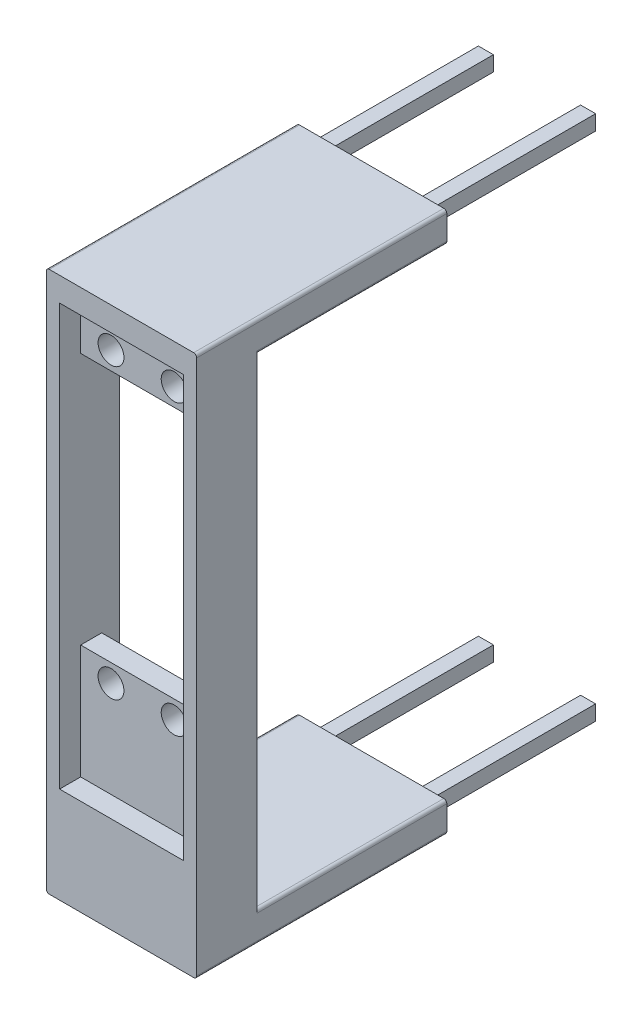
SolidWorks part; units mm, degrees
ref_plane "Front Plane" through (0, 0, 0) normal (0, 0, 1) x (1, 0, 0)
ref_plane "Top Plane" through (0, 0, 0) normal (0, 1, 0) x (1, 0, 0)
ref_plane "Right Plane" through (0, 0, 0) normal (1, 0, 0) x (0, 0, -1)
sketch "Sketch2" plane through (0, 0, -60.1331) normal (0, 0, 1) x (1, 0, 0)
  line L0 (165.5709, -7.7744) -> (110.5709, -7.7744) construction
  line L5 (113.0709, -2.7744) -> (138.0709, -2.7744)
  line L6 (113.0709, -2.7744) -> (113.0709, -7.7744)
  line L7 (113.0709, -7.7744) -> (138.0709, -7.7744)
  line L8 (138.0709, -2.7744) -> (138.0709, -7.7744)
  line L9 (110.5709, -2.7744) -> (160.5709, -2.7744) construction
  line L10 (165.5709, 82.2256) -> (110.5709, 82.2256) construction
  line L11 (113.0709, 82.2256) -> (138.0709, 82.2256)
  line L12 (113.0709, 82.2256) -> (113.0709, 77.2256)
  line L13 (113.0709, 77.2256) -> (138.0709, 77.2256)
  line L14 (138.0709, 82.2256) -> (138.0709, 77.2256)
  line L17 (115.5709, -5.2744) -> (113.0709, -5.2744)
  line L18 (115.5709, -3.7744) -> (115.5709, -6.7744) construction
  line L19 (135.5709, -5.2744) -> (138.0709, -5.2744)
  line L20 (160.5709, 77.2256) -> (110.5709, 77.2256) construction
  line L21 (135.5709, -3.7744) -> (135.5709, -6.7744) construction
  line M13 (165.5709, 82.2256) -> (110.5709, 82.2256)
  line M15 (110.5709, 77.2256) -> (160.5709, 77.2256)
  line M19 (160.5709, -2.7744) -> (110.5709, -2.7744)
  line M21 (110.5709, -7.7744) -> (165.5709, -7.7744)
  line M23 (115.5709, -3.7744) -> (118.5709, -3.7744)
  line M24 (118.5709, -3.7744) -> (118.5709, -6.7744)
  line M25 (118.5709, -6.7744) -> (115.5709, -6.7744)
  line M26 (115.5709, -6.7744) -> (115.5709, -3.7744)
  line M27 (132.5709, 81.2256) -> (135.5709, 81.2256)
  line M28 (135.5709, 81.2256) -> (135.5709, 78.2256)
  line M29 (135.5709, 78.2256) -> (132.5709, 78.2256)
  line M30 (132.5709, 78.2256) -> (132.5709, 81.2256)
  line M31 (115.5709, 81.2256) -> (118.5709, 81.2256)
  line M32 (118.5709, 81.2256) -> (118.5709, 78.2256)
  line M33 (118.5709, 78.2256) -> (115.5709, 78.2256)
  line M34 (115.5709, 78.2256) -> (115.5709, 81.2256)
  line M35 (132.5709, -3.7744) -> (135.5709, -3.7744)
  line M36 (135.5709, -3.7744) -> (135.5709, -6.7744)
  line M37 (135.5709, -6.7744) -> (132.5709, -6.7744)
  line M38 (132.5709, -6.7744) -> (132.5709, -3.7744)
  dimension "D1" = 25
extrude "Boss-Extrude1" add sketch "Sketch2" along normal up to surface (31.5956 mm away) contours L8 L6 M38 M35 M36 M19 M26 M23 M24 M25 M21 M37 | L14 L12 M13 M15 M34 M31 M32 M33 M30 M27 M28 M29 region at (125.5709, -5.2744, -60.1331) region at (125.5709, 79.7256, -60.1331)
sketch "Sketch3" plane through (0, 0, -60.1331) normal (0, 0, 1) x (1, 0, 0)
  line L0 (165.5709, -7.7744) -> (110.5709, -7.7744) construction
  line L1 (113.0709, 82.2256) -> (138.0709, 82.2256)
  line L2 (113.0709, 82.2256) -> (113.0709, -7.7744)
  line L3 (113.0709, -7.7744) -> (138.0709, -7.7744)
  line L4 (138.0709, 82.2256) -> (138.0709, -7.7744)
sketch "Sketch4" plane through (0, 0, -28.5375) normal (0, 0, 1) x (1, 0, 0)
  line L1 (113.0709, 82.2256) -> (138.0709, 82.2256)
  line L2 (113.0709, 82.2256) -> (113.0709, -7.7744)
  line L3 (113.0709, -7.7744) -> (138.0709, -7.7744)
  line L4 (138.0709, 82.2256) -> (138.0709, -7.7744)
extrude "Boss-Extrude3" add sketch "Sketch4" along normal blind 10
sketch "Sketch6" plane through (0, 0, -18.5375) normal (0, 0, 1) x (1, 0, 0)
  line L0 (113.0709, 82.2256) -> (138.0709, 82.2256) construction
  line L2 (113.0709, 82.2256) -> (113.0709, -7.7744) construction
  line L3 (138.0709, 82.2256) -> (138.0709, -7.7744) construction
  circle A2 centre (120.3209, 72.2256) radius 2.15
  circle A3 centre (130.8209, 72.2256) radius 2.15
  circle A4 centre (130.8209, 24.2256) radius 2.15
  circle A5 centre (120.3209, 24.2256) radius 2.15
  circle A6 centre (130.8209, 72.2256) radius 2.15
  point P2 (0, 0)
  point P3 (0, 0)
  point P6 (0, 0)
  point P10 (0, 0)
  dimension "D1" = 4.3
  dimension "D2" = 10
  dimension "D3" = 7.25
  dimension "D4" = 10.5
  dimension "D5" = 48
  dimension "D6" = 48
  dimension "D7" = 10.5
  dimension "D8" = 7.25
extrude "Cut-Extrude2" cut sketch "Sketch6" against normal blind 10 contours A4 | A5 | A6 | A2 region at (120.3209, 72.2256, -18.5375) region at (130.8209, 72.2256, -18.5375) region at (130.8209, 24.2256, -18.5375) region at (120.3209, 24.2256, -18.5375)
sketch "Sketch7" plane through (0, 0, -18.5375) normal (0, 0, 1) x (1, 0, 0)
  line L5 (120.3209, 24.2256) -> (120.3209, 27.2256) construction
  line L6 (135.8709, 69.2256) -> (135.8709, 27.2256)
  line L7 (115.2709, 69.2256) -> (135.8709, 69.2256)
  line L9 (115.2709, 27.2256) -> (135.8709, 27.2256)
  line L11 (115.2709, 69.2256) -> (115.2709, 27.2256)
  line L12 (138.0709, -2.7744) -> (138.0709, 77.2256) construction
  line L13 (120.3209, 72.2256) -> (120.3209, 69.2256) construction
  dimension "D1" = 20.6
  dimension "D2" = 42
  dimension "D3" = 2.2
extrude "Cut-Extrude3" cut sketch "Sketch7" against normal blind 10
sketch "Sketch8" plane through (0, 0, -60.1331) normal (0, 0, -1) x (-1, 0, 0)
  line L0 (-135.5709, -3.7744) -> (-135.5709, -6.7744) construction
  line L1 (-135.5709, 81.2256) -> (-132.5709, 81.2256)
  line L2 (-135.5709, 81.2256) -> (-135.5709, 78.2256)
  line L3 (-135.5709, 78.2256) -> (-132.5709, 78.2256)
  line L4 (-132.5709, 81.2256) -> (-132.5709, 78.2256)
  line L5 (-118.5709, 81.2256) -> (-115.5709, 81.2256)
  line L6 (-118.5709, 81.2256) -> (-118.5709, 78.2256)
  line L7 (-118.5709, 78.2256) -> (-115.5709, 78.2256)
  line L8 (-115.5709, 81.2256) -> (-115.5709, 78.2256)
  line L9 (-135.5709, -3.7744) -> (-132.5709, -3.7744)
  line L10 (-135.5709, -3.7744) -> (-135.5709, -6.7744)
  line L11 (-135.5709, -6.7744) -> (-132.5709, -6.7744)
  line L12 (-132.5709, -3.7744) -> (-132.5709, -6.7744)
  line L13 (-135.3209, 80.9756) -> (-132.8209, 78.4756)
  line L14 (-115.5709, -6.7744) -> (-118.5709, -6.7744)
  line L15 (-115.5709, -6.7744) -> (-115.5709, -3.7744)
  line L16 (-115.5709, -3.7744) -> (-118.5709, -3.7744)
  line L17 (-118.5709, -6.7744) -> (-118.5709, -3.7744)
  line L18 (-135.3209, 80.9756) -> (-132.8209, 80.9756)
  line L19 (-135.3209, 80.9756) -> (-135.3209, 78.4756)
  line L20 (-135.3209, 78.4756) -> (-132.8209, 78.4756)
  line L21 (-132.8209, 80.9756) -> (-132.8209, 78.4756)
  line L22 (-135.5709, 81.2256) -> (-132.5709, 78.2256)
  line L23 (-118.5709, 81.2256) -> (-115.5709, 78.2256) construction
  line L24 (-118.3209, 80.9756) -> (-115.8209, 80.9756)
  line L25 (-118.3209, 80.9756) -> (-118.3209, 78.4756)
  line L26 (-118.3209, 78.4756) -> (-115.8209, 78.4756)
  line L27 (-115.8209, 80.9756) -> (-115.8209, 78.4756)
  line L28 (-118.3209, 78.4756) -> (-115.8209, 80.9756)
  line L29 (-135.5709, -3.7744) -> (-132.5709, -6.7744) construction
  line L30 (-135.3209, -4.0244) -> (-132.8209, -4.0244)
  line L31 (-135.3209, -4.0244) -> (-135.3209, -6.5244)
  line L32 (-135.3209, -6.5244) -> (-132.8209, -6.5244)
  line L33 (-132.8209, -4.0244) -> (-132.8209, -6.5244)
  line L34 (-135.3209, -4.0244) -> (-132.8209, -6.5244) construction
  line L35 (-118.3209, -4.0244) -> (-115.8209, -6.5244) construction
  line L36 (-118.3209, -4.0244) -> (-115.8209, -4.0244)
  line L37 (-118.3209, -4.0244) -> (-118.3209, -6.5244)
  line L38 (-118.3209, -6.5244) -> (-115.8209, -6.5244)
  line L39 (-115.8209, -4.0244) -> (-115.8209, -6.5244)
  line L40 (-118.5709, -3.7744) -> (-115.5709, -6.7744) construction
  point P29 (-134.0709, 79.7256)
  point P30 (-134.0709, 79.7256)
  point P35 (-117.0709, 79.7256)
  point P36 (-117.0709, 79.7256)
  point P41 (-134.0709, -5.2744)
  point P42 (-134.0709, -5.2744)
  point P47 (-117.0709, -5.2744)
  point P48 (-117.0709, -5.2744)
  dimension "D1" = 2.5
  dimension "D2" = 2.5
  dimension "D3" = 2.5
  dimension "D4" = 2.5
sketch "Sketch9" plane through (138.0709, 0, 0) normal (1, 0, 0) x (0, 0, -1)
  line L0 (18.5375, 82.2256) -> (60.1331, 82.2256) construction
  line L1 (60.1331, -7.7744) -> (58.1331, -7.7744)
  line L2 (60.1331, -7.7744) -> (60.1331, 82.2256)
  line L3 (60.1331, 82.2256) -> (58.1331, 82.2256)
  line L4 (58.1331, -7.7744) -> (58.1331, 82.2256)
  dimension "D1" = 2
extrude "Cut-Extrude4" cut sketch "Sketch9" against normal through all
sketch "Sketch10" plane through (138.0709, 0, 0) normal (1, 0, 0) x (0, 0, -1)
  line L1 (58.1331, 82.2256) -> (60.1331, 82.2256)
  line L2 (58.1331, 82.2256) -> (58.1331, -7.7744)
  line L3 (58.1331, -7.7744) -> (60.1331, -7.7744)
  line L4 (60.1331, 82.2256) -> (60.1331, -7.7744)
  dimension "D1" = 2
extrude "Boss-Extrude4" add sketch "Sketch10" against normal up to surface (25 mm away) up to face at (113.0709, 37.2256, -40.8353)
extrude "Boss-Extrude5" add sketch "Sketch8" along normal blind 27.5 contours L19 L20 L13 | L21 L18 L13 | L25 L28 L24 | L28 L26 L27 | L39 L36 L37 L38 | L33 L30 L31 L32 region at (133.6542, 80.1423, -60.1331) region at (134.4876, 79.309, -60.1331) region at (117.4876, 80.1423, -60.1331) region at (116.6542, 79.309, -60.1331) region at (134.0709, -5.2744, -60.1331) region at (117.0709, -5.2744, -60.1331)
sketch "Sketch11" plane through (138.0709, 0, 0) normal (1, 0, 0) x (0, 0, -1)
  line L1 (58.1331, 77.2256) -> (61.1331, 77.2256)
  line L2 (58.1331, 77.2256) -> (58.1331, -2.7744)
  line L3 (58.1331, -2.7744) -> (61.1331, -2.7744)
  line L4 (61.1331, 77.2256) -> (61.1331, -2.7744)
  dimension "D1" = 3
extrude "Cut-Extrude5" cut sketch "Sketch11" against normal through all
sketch "Sketch13" plane through (0, 0, -28.5375) normal (0, 0, -1) x (-1, 0, 0)
  line L1 (-135.8709, 75.4756) -> (-115.2709, 75.4756)
  line L2 (-135.8709, 75.4756) -> (-135.8709, 18.4756)
  line L3 (-135.8709, 18.4756) -> (-115.2709, 18.4756)
  line L4 (-115.2709, 75.4756) -> (-115.2709, 18.4756)
  line L8 (-135.8709, 69.2256) -> (-115.2709, 69.2256) construction
  line L9 (-115.2709, 27.2256) -> (-135.8709, 27.2256) construction
  line L10 (-135.8709, 27.2256) -> (-135.8709, 69.2256) construction
  dimension "D1" = 6.25
  dimension "D2" = 8.75
  dimension "D3" = 20.6
extrude "Cut-Extrude6" cut sketch "Sketch13" against normal blind 3
fillet "Fillet1" radius 0.5 8 edges at (138.0709, 82.2256, -39.3353) (138.0709, -7.7744, -39.3353) (113.0709, -7.7744, -39.3353) (113.0709, 82.2256, -39.3353) (113.0709, 77.2256, -44.3353) (113.0709, -2.7744, -44.3353) (138.0709, 77.2256, -44.3353) (138.0709, -2.7744, -44.3353)
sketch "Sketch14" plane through (0, 0, -18.5375) normal (0, 0, 1) x (1, 0, 0)
  line L0 (137.5709, 82.2256) -> (113.5709, 82.2256) construction
  line L1 (115.2709, 78.2256) -> (135.8709, 78.2256)
  line L2 (115.2709, 78.2256) -> (115.2709, 8.2256)
  line L3 (115.2709, 8.2256) -> (135.8709, 8.2256)
  line L4 (135.8709, 78.2256) -> (135.8709, 8.2256)
  line L5 (113.0709, 81.7256) -> (113.0709, -7.2744) construction
  dimension "D1" = 70
  dimension "D2" = 20.6
  dimension "D3" = 4
  dimension "D4" = 2.2
extrude "Cut-Extrude7" cut sketch "Sketch14" against normal blind 3.5
